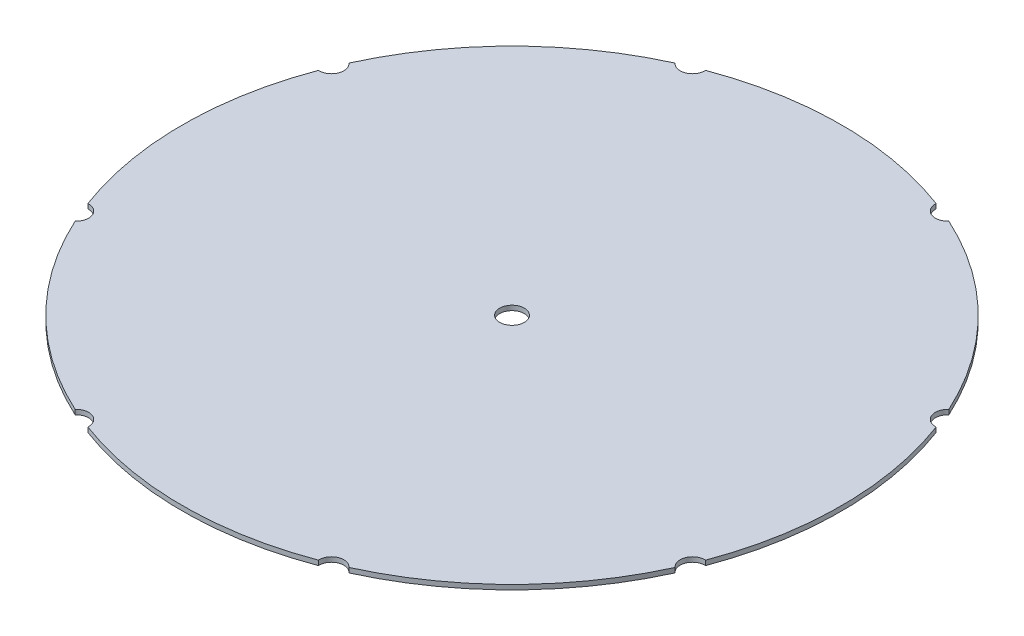
SolidWorks part; units mm, degrees
ref_plane "Front Plane" through (0, 0, 0) normal (0, 0, 1) x (1, 0, 0)
ref_plane "Top Plane" through (0, 0, 0) normal (0, 1, 0) x (1, 0, 0)
ref_plane "Right Plane" through (0, 0, 0) normal (1, 0, 0) x (0, 0, -1)
sketch "Sketch2" plane through (0, 0, 0) normal (1, 0, 0) x (0, 0, -1)
  line L0 (0, 0) -> (-69.2, 0)
  line L1 (-69.2, 0) -> (-69.2, 1)
  line L2 (-69.2, 1) -> (0, 1)
  line L5 (0, 1) -> (0, 0)
  dimension "D1" = 69.2
  dimension "D2" = 1
ref_axis "Axis1" through (0, -0.05, 0) along (0, 1, 0)
revolve "Revolve1" add sketch "Sketch2" angle 360 about axis through (0, -0.05, 0) along (0, 1, 0)
hole_wizard "#6 (0.204) Diameter Hole1" positions "Sketch6" profile "Sketch7" hole size "#6" standard "ANSI Inch" end condition through all
sketch "Sketch6" plane through (0, 1, 0) normal (0, 1, 0) x (1, 0, 0)
  line L0 (0, 0) -> (-53.438, 129.0108) construction
  line L2 (0, 0) -> (0, 109.0908) construction
  point P0 (-26.7878, 64.6716)
  dimension "D1" = 22.5
  dimension "D2" = 70
sketch "Sketch7" plane through (-26.7878, 1, -64.6716) normal (1, 0, 0) x (0, 0, 1)
  line L0 (0, 0) -> (0, 1)
  line L1 (0, 1) -> (2.5908, 1)
  line L2 (2.5908, 1) -> (2.5908, 0)
  line L5 (2.5908, 0) -> (0, 0)
  line L11 (0, -6.35) -> (0, 107.95) construction
  dimension "Thru Hole Dia." = 5.1816
  dimension "Thru Hole Depth" = 1
pattern_circular "CirPattern3" count 8 over 360 about axis through (0, -0.05, 0) along (0, 1, 0) of "#6 (0.204) Diameter Hole1"
hole_wizard "#6 (0.204) Diameter Hole2" positions "Sketch8" profile "Sketch9" hole size "#6" standard "ANSI Inch" end condition through all
sketch "Sketch8" plane through (0, 1, 0) normal (0, 1, 0) x (1, 0, 0)
  line L0 (0, 0) -> (106.3094, -1.7118) construction
  point P7 (0, 0)
sketch "Sketch9" plane through (0, 1, 0) normal (1, 0, 0) x (0, 0, 1)
  line L0 (0, 0) -> (0, 1)
  line L1 (0, 1) -> (2.5908, 1)
  line L2 (2.5908, 1) -> (2.5908, 0)
  line L5 (2.5908, 0) -> (0, 0)
  line L11 (0, -6.35) -> (0, 107.95) construction
  dimension "Thru Hole Dia." = 5.1816
  dimension "Thru Hole Depth" = 1
equation "\"TubeDiameter\" = 6.000in"
equation "\"D1@Sketch2\"=\"TubeDiameter\"/2-7mm"
